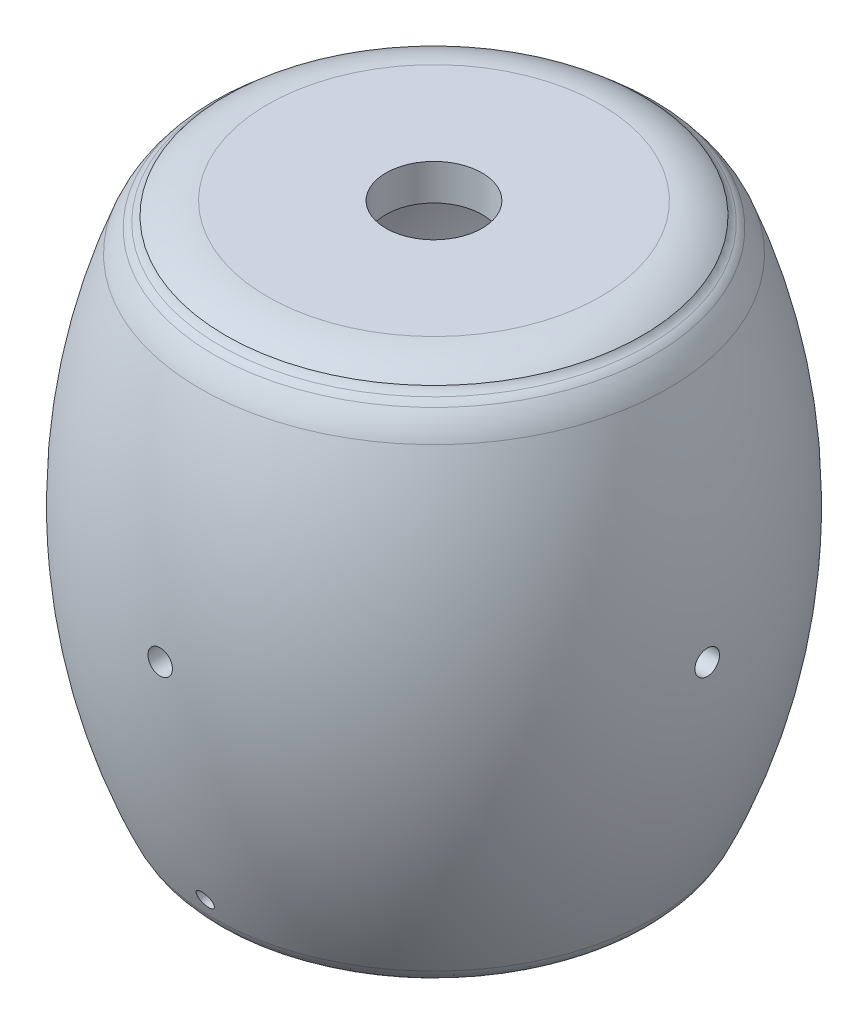
SolidWorks part; units mm, degrees
ref_plane "Front Plane" through (0, 0, 0) normal (0, 0, 1) x (1, 0, 0)
ref_plane "Top Plane" through (0, 0, 0) normal (0, 1, 0) x (1, 0, 0)
ref_plane "Right Plane" through (0, 0, 0) normal (1, 0, 0) x (0, 0, -1)
sketch "Sketch2" plane through (0, 0, 0) normal (0, 0, 1) x (1, 0, 0)
  line L1 (-142.8245, 0) -> (143.6743, 0) construction
  line L2 (-202.362, 110.7345) -> (365.1962, 110.7345) construction
  line L3 (0, -20) -> (-90, -20) construction
  line L4 (-90, -83.4454) -> (-90, 331.1943) construction
  line L8 (-20.6932, 220) -> (-90, 220)
  line L9 (-20.6932, 205) -> (-90, 205)
  line L10 (-90, 220) -> (-90, 205)
  line L11 (-4.9262, 0) -> (-19.2818, 0)
  line L12 (-19.2818, 0) -> (-19.2818, 12.4799)
  line L13 (-19.2818, 12.4799) -> (-12.1346, 13.1544)
  arc A0 (1.5112, 6.9259) -> (7.2919, 200.8089) centre (-225.9175, 110.7345) ccw
  arc A2 (1.5112, 6.9259) -> (-4.9262, 0) centre (-12.1346, 13.1544) cw
  arc A10 (-12.1346, 13.1544) -> (-12.1346, 13.1544) centre (-12.1346, 13.1544) cw
  arc A11 (-12.1346, 13.1544) -> (-6.7007, 195.4045) centre (-225.9175, 110.7345) ccw
  arc A12 (-20.6932, 205) -> (-6.7007, 195.4045) centre (-20.6932, 190) cw
  arc A17 (1.5294, 210.1533) -> (7.2919, 200.8089) centre (-20.6932, 190) cw
  arc A18 (-20.6932, 220) -> (-3.4461, 214.5466) centre (-20.6932, 190) cw
  arc A19 (-3.4461, 214.5466) -> (-1.0214, 212.1769) centre (2.1016, 217.7977) ccw
  arc A20 (-20.6932, 220) -> (7.2919, 200.8089) centre (-20.6932, 190) cw construction
  arc A21 (1.5294, 210.1533) -> (-1.0214, 212.1769) centre (-5.8781, 203.4355) ccw
  point P0 (0, 0)
  point P11 (-86.4792, 156.5384)
  point P13 (-4.944, -0.0828)
  point P14 (0, 0)
  point P29 (0, 0)
  point P30 (-6.5748, 7.2962)
  point P31 (-86.4792, 156.5384)
  point P32 (-89.8547, -12.7145)
  point P50 (0, 211.7207)
  point P51 (-198.3178, 259.5466)
  point P52 (-11.6501, 294.9746)
  point P53 (-13.1897, 216.7966)
  dimension "D3" = 250
  dimension "D7" = 15
  dimension "D1" = 30
  dimension "D4" = 220
  dimension "D12" = 10
  dimension "D2" = 90
  dimension "D5" = 20
revolve "Revolve1" add sketch "Sketch2" angle 360 about L4 region at (-12.396, 216.2413, 0)
sketch "Sketch3" plane through (0, 0, 0) normal (0, -1, 0) x (1, 0, 0)
  circle A0 centre (-90, 0) radius 77.5012
  circle A1 centre (-90, 0) radius 81
  dimension "D1" = 155.0025
  dimension "D2" = 162
extrude "Cut-Extrude1" cut sketch "Sketch3" against normal blind 20
revolve "Revolve2" add sketch "Sketch2<3>" angle 360 about L4 region at (-12.396, 216.2413, 0)
sketch "Sketch2<3>" plane through (0, 0, 0) normal (0, 0, 1) x (1, 0, 0) same geometry as "Sketch2"
ref_plane "Plane1" through (0, 0, 91.7) normal (0, 0, 1) x (1, 0, 0)
sketch "Sketch5" plane through (0, 220, 0) normal (0, 1, 0) x (1, 0, 0)
  circle A0 centre (-90, 0) radius 20
  dimension "D1" = 40
extrude "Cut-Extrude3" cut sketch "Sketch5" against normal blind 20
sketch "Sketch6" plane through (0, 0, 91.7) normal (0, 0, 1) x (1, 0, 0)
  line L0 (-90, 0) -> (-90, 330) construction
  line L1 (-175.0738, 0) -> (-4.9262, 0) construction
  line L2 (-204.0825, 110.7345) -> (38.389, 110.7345) construction
  arc A0 (-187.2919, 200.8089) -> (-181.5112, 6.9259) centre (45.9175, 110.7345) ccw construction
  circle A1 centre (-90, 110.7345) radius 5.1
  dimension "D1" = 10.2
extrude "Cut-Extrude4" cut sketch "Sketch6" against normal blind 410 and the other way blind 30
sketch "Sketch7" plane through (0, 0, 0) normal (1, 0, 0) x (0, 0, -1)
  line L0 (0, 330) -> (0, 0) construction
  line L1 (-113.8915, 110.7345) -> (113.402, 110.7345) construction
  circle A0 centre (-0.2448, 110.7345) radius 5.1
  dimension "D1" = 10.2
extrude "Cut-Extrude5" cut sketch "Sketch7" against normal through all both and the other way through all
sketch "Sketch8" plane through (0, 0, 91.7) normal (0, 0, 1) x (1, 0, 0)
  line L0 (-90, 0) -> (-90, 330) construction
  line L1 (-175.0738, 0) -> (-4.9262, 0) construction
  circle A0 centre (-90, 15.6297) radius 3.55
  dimension "D1" = 7.1
extrude "Cut-Extrude6" cut sketch "Sketch8" against normal blind 12 and the other way through all
